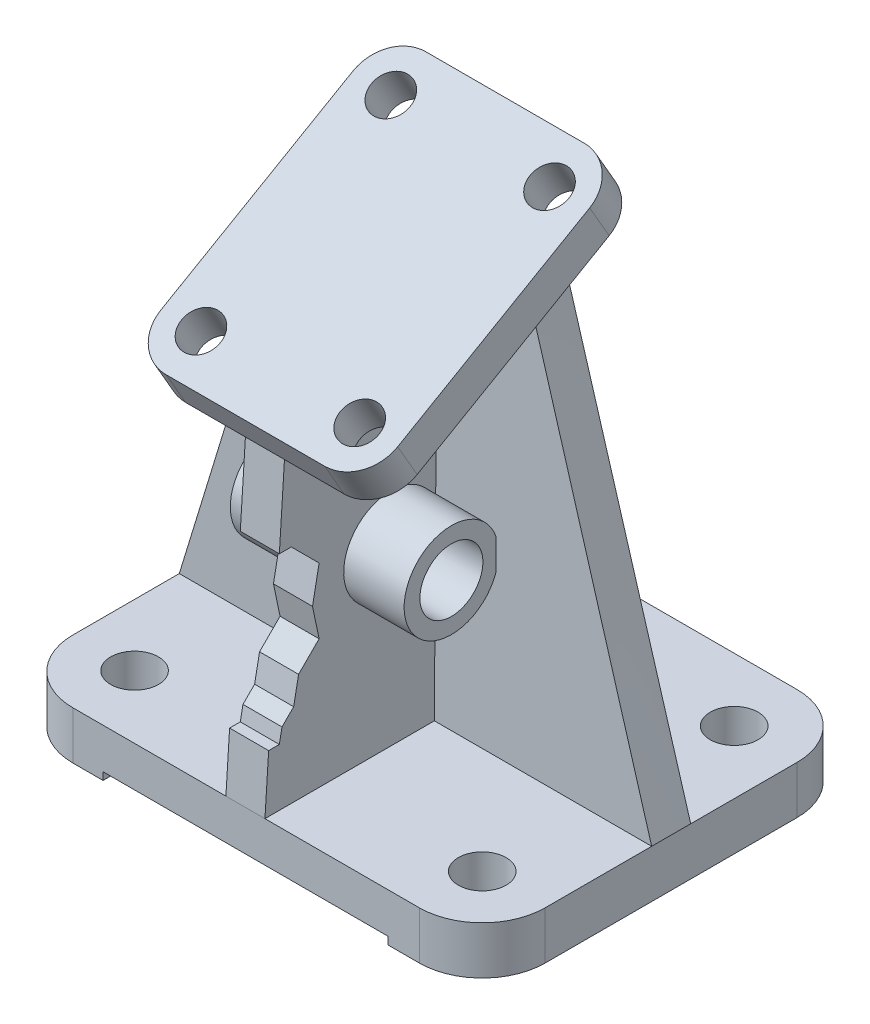
SolidWorks part; units mm, degrees
ref_plane "Front Plane" through (0, 0, 0) normal (0, 0, 1) x (1, 0, 0)
ref_plane "Top Plane" through (0, 0, 0) normal (0, 1, 0) x (1, 0, 0)
ref_plane "Right Plane" through (0, 0, 0) normal (1, 0, 0) x (0, 0, -1)
sketch "Sketch2" plane through (0, 0, 0) normal (0, 1, 0) x (1, 0, 0)
  line L0 (-73.7789, 0) -> (97.2299, 0) construction
  line L1 (35.052, -38.1) -> (-34.798, -38.1)
  line L2 (47.752, -25.4) -> (47.752, 25.4)
  line L3 (35.052, 38.1) -> (-34.798, 38.1)
  line L4 (-47.498, -25.4) -> (-47.498, 25.4)
  line L5 (0, -60.2157) -> (0, 80.6527) construction
  circle A0 centre (35.052, 25.4) radius 4.826
  circle A1 centre (35.052, -25.4) radius 4.826
  circle A2 centre (-35.052, -25.4) radius 4.826
  arc A3 (-34.798, -38.1) -> (-47.498, -25.4) centre (-34.798, -25.4) cw
  arc A4 (-34.798, 38.1) -> (-47.498, 25.4) centre (-34.798, 25.4) ccw
  arc A5 (47.752, 25.4) -> (35.052, 38.1) centre (35.052, 25.4) ccw
  arc A6 (35.052, -38.1) -> (47.752, -25.4) centre (35.052, -25.4) ccw
  circle A7 centre (-35.052, 25.4) radius 4.826
  point P0 (0, 0)
  point P20 (-47.498, 38.1)
  point P23 (47.752, 38.1)
  point P26 (47.752, -38.1)
  dimension "D3" = 9.652
  dimension "D4" = 12.7
  dimension "D5" = 12.7
  dimension "D6" = 35.052
  dimension "D7" = 12.7
  dimension "D1" = 95.25
  dimension "D2" = 76.2
extrude "Boss-Extrude1" add sketch "Sketch2" along normal blind 9.652
sketch "Sketch4" plane through (0, 0, 38.1) normal (0, 0, 1) x (1, 0, 0)
  line L0 (0, -19.6069) -> (0, 0) construction
  line L2 (28.702, 0) -> (28.702, 1.524)
  line L3 (-34.798, 0) -> (35.052, 0) construction
  line L4 (28.702, 1.524) -> (-28.702, 1.524)
  line L6 (-28.702, 0) -> (28.702, 0)
  line L7 (0, 1.524) -> (0, 27.19) construction
  line L8 (-28.702, 0) -> (-28.702, 1.524)
  dimension "D1" = 28.702
  dimension "D2" = 1.524
extrude "Cut-Extrude1" cut sketch "Sketch4" against normal up to next
sketch "Sketch5" plane through (0, 0, 0) normal (1, 0, 0) x (0, 0, -1)
  line L0 (-38.1, 9.652) -> (-38.1, 77.216) construction
  line L1 (-38.1, 77.216) -> (-9.3501, 93.8147) construction
  dimension "D1" = 67.564
  dimension "D2" = 120
ref_plane "Plane1" through (0, 74.4098, 42.9605) normal (0, -0.866, -0.5) x (0, 0.5, -0.866)
sketch "Sketch7" plane through (0, 74.4098, 42.9605) normal (0, -0.866, -0.5) x (0, 0.5, -0.866)
  line L1 (13.4864, -23.876) -> (58.1904, -23.876)
  line L2 (5.6124, -16.002) -> (5.6124, 16.002)
  line L3 (13.4864, 23.876) -> (58.1904, 23.876)
  line L4 (66.0644, -16.002) -> (66.0644, 16.002)
  line L8 (35.8384, -30.4721) -> (35.8384, 44.8781) construction
  line L9 (76.1265, 0) -> (5.6124, 0) construction
  circle A0 centre (13.7404, 16.002) radius 3.937
  circle A1 centre (13.7404, -16.002) radius 3.937
  circle A2 centre (57.9364, -16.002) radius 3.937
  circle A3 centre (57.9364, 16.002) radius 3.937
  arc A4 (58.1904, 23.876) -> (66.0644, 16.002) centre (58.1904, 16.002) cw
  arc A5 (58.1904, -23.876) -> (66.0644, -16.002) centre (58.1904, -16.002) ccw
  arc A6 (13.4864, -23.876) -> (5.6124, -16.002) centre (13.4864, -16.002) cw
  arc A7 (5.6124, 16.002) -> (13.4864, 23.876) centre (13.4864, 16.002) cw
  point P0 (35.8384, 0)
  point P20 (66.0644, 23.876)
  point P23 (66.0644, -23.876)
  point P28 (5.6124, 23.876)
  dimension "D3" = 7.874
  dimension "D4" = 16.002
  dimension "D5" = 22.098
  dimension "D6" = 7.874
  dimension "D1" = 60.452
  dimension "D2" = 47.752
  dimension "D7" = 30.226
extrude "Boss-Extrude2" add sketch "Sketch7" along normal blind 7.874 separate body
sketch "Sketch8" plane through (0, 9.652, 0) normal (0, 1, 0) x (1, 0, 0)
  line L0 (47.752, -25.4) -> (47.752, 25.4) construction
  line L1 (47.752, -3.937) -> (-47.498, -3.937)
  line L2 (47.752, -3.937) -> (47.752, 3.937)
  line L3 (47.752, 3.937) -> (-47.498, 3.937)
  line L4 (-47.498, -3.937) -> (-47.498, 3.937)
  line L5 (-47.498, 25.4) -> (-47.498, -25.4) construction
  line L6 (-47.498, 0) -> (47.752, 0) construction
  line L7 (35.052, 38.1) -> (-34.798, 38.1) construction
  dimension "D1" = 7.874
  dimension "D2" = 38.1
sketch "Sketch9" plane through (0, 0, 0) normal (0, 0, 1) x (1, 0, 0)
  line L0 (47.752, 9.652) -> (23.876, 90.1209)
  line L1 (-47.498, 9.652) -> (47.752, 9.652) construction
sketch "Sketch10" plane through (0, 67.5907, 39.0235) normal (0, -0.866, -0.5) x (1, 0, 0)
  line L0 (23.876, -58.1904) -> (23.876, -13.4864) construction
  line L1 (23.876, -48.9863) -> (-23.876, -48.9863)
  line L2 (23.876, -48.9863) -> (23.876, -41.1346)
  line L3 (23.876, -41.1346) -> (-23.876, -41.1346)
  line L4 (-23.876, -48.9863) -> (-23.876, -41.1346)
  line L5 (-23.876, -13.4864) -> (-23.876, -58.1904) construction
  dimension "D1" = 7.8517
loft "Loft1" add profiles "Sketch10", "Sketch8"
sketch "Sketch11" plane through (0, 0, 0) normal (1, 0, 0) x (0, 0, -1)
  line L0 (-38.1, 9.652) -> (-34.163, 70.3969)
rib "Rib1" sketch "Sketch11" sketch "Sketch11" thickness 7.874 extrusion direction parallel to sketch draft on no parameters "D1"=7.874
sketch "Sketch12" plane through (-3.937, 0, 0) normal (-1, 0, 0) x (0, 0, 1)
  line L0 (3.937, 9.652) -> (25.4, 9.652) construction
  circle A0 centre (12.7, 44.704) radius 9.525
  circle A1 centre (12.7, 44.704) radius 6.35
  point P5 (0, 0)
  point P7 (12.0805, 41.9281)
  dimension "D1" = 19.05
  dimension "D2" = 12.7
  dimension "D3" = 35.052
  dimension "D4" = 12.7
extrude "Boss-Extrude3" add sketch "Sketch12" along normal blind 14.986 and the other way blind 20.066 contours A0
extrude "Cut-Extrude2" cut sketch "Sketch12<3>" against normal through all both and the other way through all contours A1
sketch "Sketch12<3>" plane through (-3.937, 0, 0) normal (-1, 0, 0) x (0, 0, 1) same geometry as "Sketch12"
sketch "Sketch13" plane through (-3.937, 0, 0) normal (-1, 0, 0) x (0, 0, 1)
  line L2 (32.79, 54.4469) -> (29.8383, 51.4953)
  line L3 (29.8383, 51.4953) -> (27.1777, 48.8347)
  line L4 (27.1777, 48.8347) -> (28.508, 41.9281)
  line L5 (28.508, 41.9281) -> (27.1777, 35.6002)
  line L6 (27.1777, 35.6002) -> (31.3141, 31.4638)
  line L7 (31.3141, 31.4638) -> (32.3081, 26.3032)
  line L8 (32.3081, 26.3032) -> (34.6599, 23.9515)
  line L9 (34.6599, 23.9515) -> (35.1968, 21.1642)
  line L10 (35.1968, 21.1642) -> (41.1313, 21.1642)
  line L11 (41.1313, 21.1642) -> (39.1178, 54.4469)
  line L13 (39.1178, 54.4469) -> (32.79, 54.4469)
extrude "Cut-Extrude3" cut sketch "Sketch13" against normal up to next
